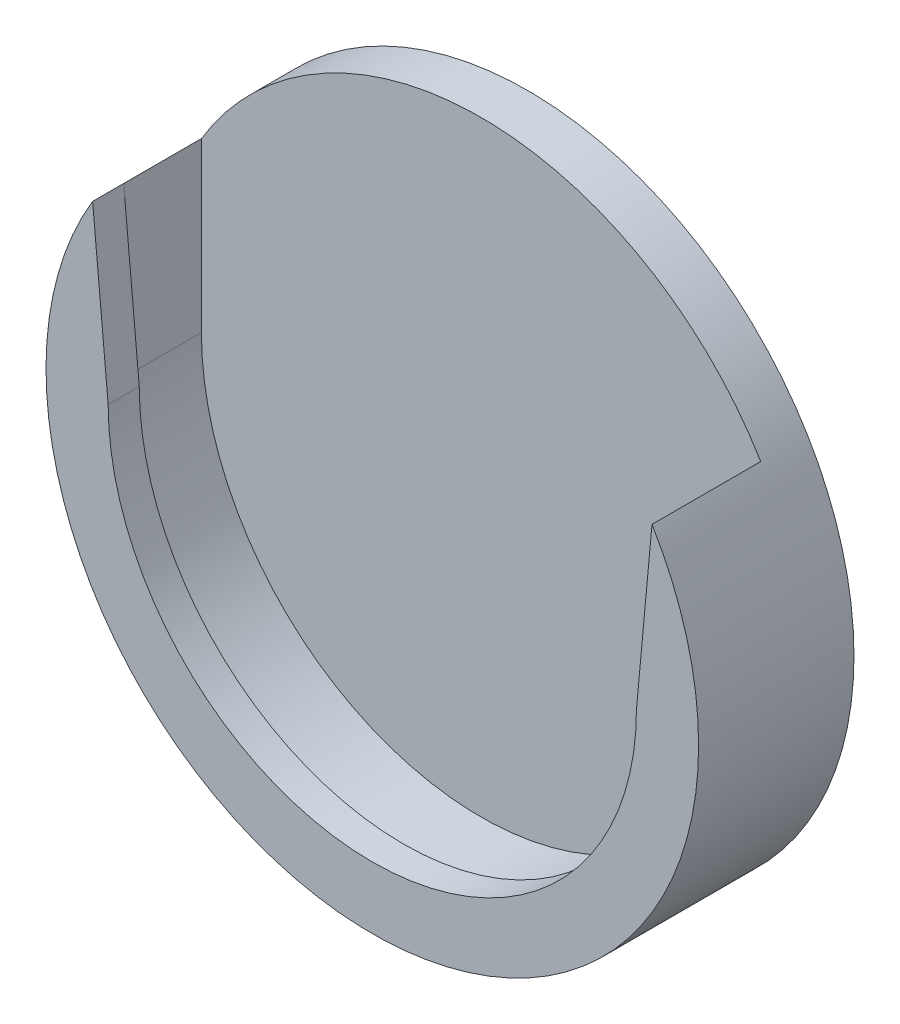
SolidWorks part; units mm, degrees
ref_plane "Plano frontal" through (0, 0, 0) normal (0, 0, 1) x (1, 0, 0)
ref_plane "Plano superior" through (0, 0, 0) normal (0, 1, 0) x (1, 0, 0)
ref_plane "Plano direito" through (0, 0, 0) normal (1, 0, 0) x (0, 0, -1)
sketch "Esboço1" plane through (0, 0, 0) normal (0, 0, 1) x (1, 0, 0)
  line L0 (-18, 0) -> (-18, 10.8167)
  line L2 (18, 10.8167) -> (18, 0)
  circle A0 centre (0, 0) radius 18
  circle A1 centre (0, 0) radius 21
extrude "Ressalto-extrusão1" add sketch "Esboço1" against normal blind 3 contours L2 A1 L0 A0 | A0 | L0 A1 L2 A0 region at (0, -18.5269, 0) region at (-17.5832, 5.4083, 0) region at (0, 0, 0)
extrude "Ressalto-extrusão2" add sketch "Esboço1<3>" along normal blind 5 contours L0 A1 L2 A0 region at (0, -18.5269, 0)
sketch "Esboço1<3>" plane through (0, 0, 0) normal (0, 0, 1) x (1, 0, 0) same geometry as "Esboço1"
sketch "Esboço3" plane through (0, 0, 5) normal (0, 0, 1) x (1, 0, 0)
  line L0 (-18, 10.8167) -> (-17, 0)
  line L1 (-17, 0) -> (17, 0)
  line L2 (17, 0) -> (18, 10.8167)
  circle A0 centre (0, 0) radius 21
  circle A1 centre (0, 0) radius 18
  circle A2 centre (0, 0) radius 17
  line M4 (-18, 0) -> (-18, 10.8167)
  arc M5 (-18, 10.8167) -> (18, 10.8167) centre (0, 0) ccw
  line M6 (18, 10.8167) -> (18, 0)
  arc M7 (18, 0) -> (-18, 0) centre (0, 0) cw
extrude "Ressalto-extrusão3" add sketch "Esboço3" along normal blind 2 contours A2 L0 A1 L2 M7 | M7 M4 M5 M6 | A1 L0 M4 | A1 L2 M6 region at (-18.5269, 5.4083, 5) region at (-17.8128, 5.5861, 5) region at (-17.6326, 2.2285, 5) region at (17.8128, 5.5861, 5)
sketch "Esboço4" plane through (0, 0, 7) normal (0, 0, 1) x (1, 0, 0)
  circle A0 centre (0, 0) radius 16
